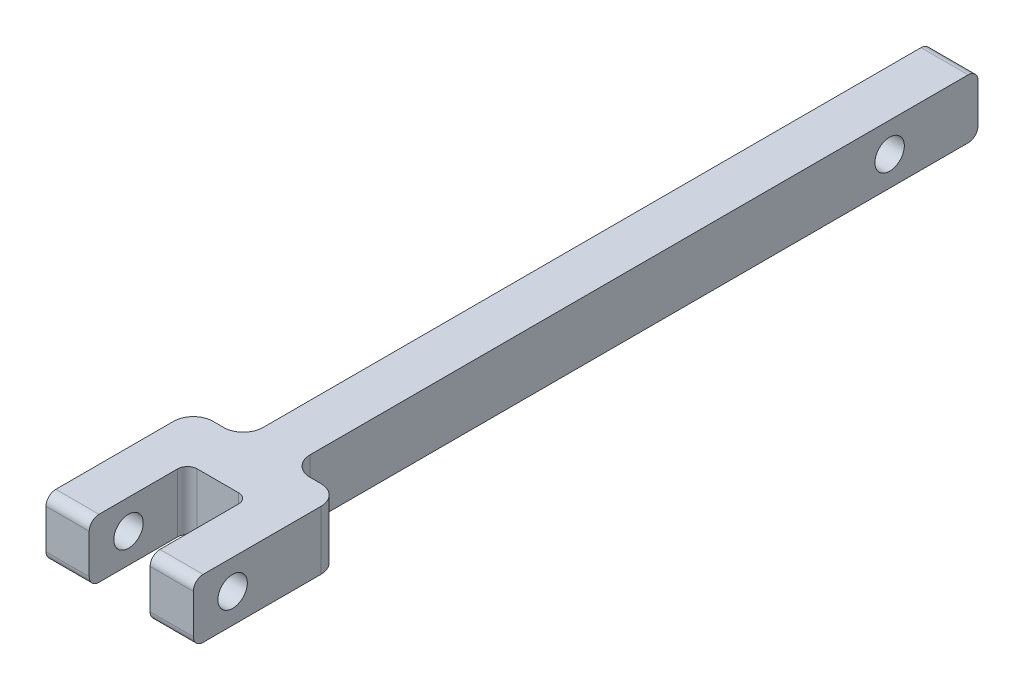
SolidWorks part; units mm, degrees
ref_plane "Alzado" through (0, 0, 0) normal (0, 0, 1) x (1, 0, 0)
ref_plane "Planta" through (0, 0, 0) normal (0, 1, 0) x (1, 0, 0)
ref_plane "Vista lateral" through (0, 0, 0) normal (1, 0, 0) x (0, 0, -1)
sketch "Croquis1" plane through (0, 0, 0) normal (1, 0, 0) x (0, 0, -1)
  line L0 (-41.5, 3) -> (41.5, 3)
  line L2 (-42.5, 0) -> (42.5, 0) construction
  line L3 (-42.5, 2) -> (-42.5, -2)
  line L4 (-41.5, -3) -> (41.5, -3)
  line L5 (42.5, 2) -> (42.5, -2)
  arc A0 (-42.5, -2) -> (-41.5, -3) centre (-41.5, -2) ccw
  arc A1 (-42.5, 2) -> (-41.5, 3) centre (-41.5, 2) cw
  arc A2 (41.5, -3) -> (42.5, -2) centre (41.5, -2) ccw
  arc A3 (41.5, 3) -> (42.5, 2) centre (41.5, 2) cw
  point P1 (0, 0)
  point P9 (-42.5, -3)
  point P13 (-42.5, 3)
  point P16 (42.5, -3)
  point P19 (42.5, 3)
  dimension "D3" = 1
  dimension "D4" = 1
  dimension "D1" = 3
  dimension "D2" = 85
extrude "Saliente-Extruir1" add sketch "Croquis1" along normal mid plane 4.8
sketch "Croquis2" plane through (0, 0, 0) normal (1, 0, 0) x (0, 0, -1)
  line L0 (-42.5, 2) -> (-42.5, -2) construction
  line L1 (42.5, -2) -> (42.5, 2) construction
  circle A0 centre (-38.5, 0) radius 1.5
  circle A1 centre (33.5, 0) radius 1.5
  dimension "D1" = 3
  dimension "D3" = 3
  dimension "D2" = 4
  dimension "D4" = 9
extrude "Cortar-Extruir1" cut sketch "Croquis2" against normal through all both and the other way through all
sketch "Croquis3" plane through (0, 0, 0) normal (1, 0, 0) x (0, 0, -1)
  line L0 (-42.5, 2) -> (-42.5, -2) construction
  line L1 (-42.5, 2) -> (-42.5, -2)
  line L2 (-41.5, 3) -> (-27.5, 3)
  line L3 (41.5, 3) -> (-41.5, 3) construction
  line L4 (-27.5, 3) -> (-27.5, -3)
  line L5 (-41.5, -3) -> (41.5, -3) construction
  line L6 (-27.5, -3) -> (-41.5, -3)
  circle A0 centre (-38.5, 0) radius 1.5 construction
  circle A1 centre (-38.5, 0) radius 1.5
  arc A2 (-41.5, 3) -> (-42.5, 2) centre (-41.5, 2) ccw construction
  arc A3 (-41.5, 3) -> (-42.5, 2) centre (-41.5, 2) ccw
  arc A4 (-42.5, -2) -> (-41.5, -3) centre (-41.5, -2) ccw construction
  arc A5 (-42.5, -2) -> (-41.5, -3) centre (-41.5, -2) ccw
  dimension "D1" = 15
extrude "Saliente-Extruir2" add sketch "Croquis3" along normal mid plane 15
sketch "Croquis4" plane through (0, 0, 0) normal (1, 0, 0) x (0, 0, -1)
  line L0 (-41.5, 3) -> (-32.5, 3)
  line L1 (-27.5, 3) -> (-41.5, 3) construction
  line L2 (-32.5, 3) -> (-32.5, -3)
  line L3 (-41.5, -3) -> (-27.5, -3) construction
  line L4 (-42.5, 2) -> (-42.5, -2)
  line L5 (-41.5, -3) -> (-27.5, -3)
  line L6 (-27.5, -3) -> (-27.5, 3)
  line L7 (-27.5, 3) -> (-41.5, 3)
  line L8 (-42.5, 2) -> (-42.5, -2)
  line L12 (-32.5, -3) -> (-41.5, -3)
  arc A2 (-41.5, 3) -> (-42.5, 2) centre (-41.5, 2) ccw
  arc A3 (-42.5, -2) -> (-41.5, -3) centre (-41.5, -2) ccw
  arc A4 (-41.5, 3) -> (-42.5, 2) centre (-41.5, 2) ccw
  arc A5 (-42.5, -2) -> (-41.5, -3) centre (-41.5, -2) ccw
  dimension "D2" = 10
  dimension "D1" = 0
extrude "Cortar-Extruir2" cut sketch "Croquis4" against normal mid plane 6.2
fillet "Redondeo1" radius 2 4 edges at (2.4, 0, 27.5) (-2.4, 0, 27.5) (7.5, 0, 27.5) (-7.5, 0, 27.5)
fillet "Redondeo2" radius 1 2 edges at (3.1, 0, 32.5) (-3.1, 0, 32.5)
